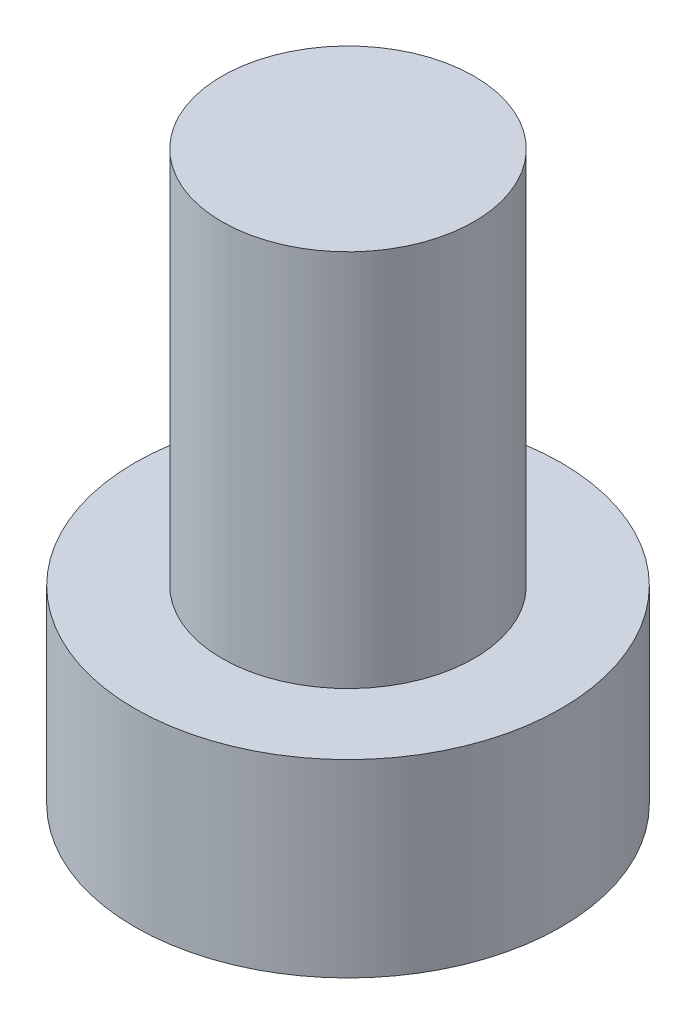
SolidWorks part; units mm, degrees
ref_plane "Front Plane" through (0, 0, 0) normal (0, 0, 1) x (1, 0, 0)
ref_plane "Top Plane" through (0, 0, 0) normal (0, 1, 0) x (1, 0, 0)
ref_plane "Right Plane" through (0, 0, 0) normal (1, 0, 0) x (0, 0, -1)
sketch "Sketch1" plane through (0, 0, 0) normal (0, 1, 0) x (1, 0, 0)
  circle A0 centre (0, 0) radius 3.38
  circle A1 centre (0, 0) radius 2
extrude "Boss-Extrude1" add sketch "Sketch1" along normal blind 3
extrude "Boss-Extrude2" add sketch "Sketch1<2>" along normal blind 9 contours A1 region at (0, 0, 0)
sketch "Sketch1<2>" plane through (0, 0, 0) normal (0, 1, 0) x (1, 0, 0) same geometry as "Sketch1"
